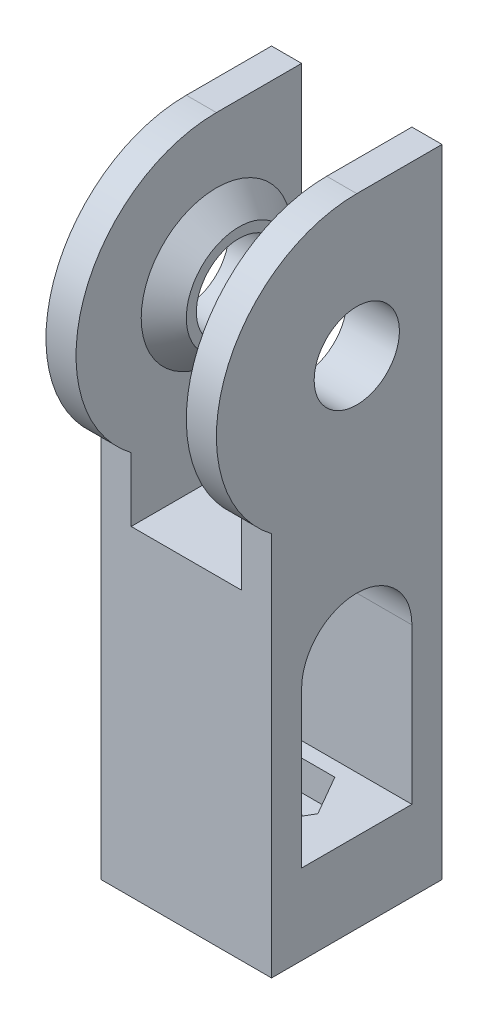
SolidWorks part; units mm, degrees
ref_plane "Front Plane" through (0, 0, 0) normal (0, 0, 1) x (1, 0, 0)
ref_plane "Top Plane" through (0, 0, 0) normal (0, 1, 0) x (1, 0, 0)
ref_plane "Right Plane" through (0, 0, 0) normal (1, 0, 0) x (0, 0, -1)
sketch "Sketch1" plane through (0, 0, 0) normal (0, 0, 1) x (1, 0, 0)
  line L0 (8.5, 32) -> (8.5, 0) construction
  line L1 (0, 0) -> (17, 0)
  line L2 (0, 0) -> (0, 63.5)
  line L3 (0, 63.5) -> (3, 63.5)
  line L4 (17, 0) -> (17, 63.5)
  line L5 (14, 63.5) -> (17, 63.5)
  line L6 (3, 63.5) -> (3, 32)
  line L7 (3, 32) -> (14, 32)
  line L8 (14, 63.5) -> (14, 32)
  dimension "D1" = 63.5
  dimension "D2" = 17
  dimension "D3" = 11
  dimension "D4" = 31.5
extrude "Boss-Extrude1" add sketch "Sketch1" along normal blind 22.5
sketch "Sketch2" plane through (17, 0, 0) normal (1, 0, 0) x (0, 0, -1)
  line L0 (-8.5, 8) -> (-8.5, 0) construction
  line L1 (-14, 23.5) -> (-3, 23.5) construction
  line L2 (-14, 23.5) -> (-14, 8)
  line L3 (-14, 8) -> (-3, 8)
  line L4 (-3, 23.5) -> (-3, 8)
  line L6 (-22.5, 0) -> (0, 0) construction
  line L7 (-8.5, 23.5) -> (-8.5, 49.5) construction
  line L8 (0, 0) -> (0, 63.5) construction
  line L9 (-22.5, 63.5) -> (-8.5, 63.5)
  line L10 (-22.5, 63.5) -> (0, 63.5) construction
  line L11 (-22.5, 63.5) -> (-22.5, 49.5)
  line L12 (-22.5, 0) -> (-22.5, 63.5) construction
  line L13 (-22.5, 0) -> (-22.5, 49.5)
  line L14 (-17, 38.3757) -> (-17, 0)
  line L15 (-22.5, 0) -> (-17, 0)
  arc A0 (-14, 23.5) -> (-3, 23.5) centre (-8.5, 23.5) cw
  circle A1 centre (-8.5, 49.5) radius 4.25 construction
  arc A2 (-8.5, 63.5) -> (-17, 38.3757) centre (-8.5, 49.5) ccw
  point P29 (-17, 19.1879)
  line M9 (0, 63.5) -> (-22.5, 63.5)
  line M10 (-22.5, 63.5) -> (-22.5, 0)
  line M11 (-22.5, 0) -> (0, 0)
  dimension "D3" = 5.5
  dimension "D5" = 8.5
  dimension "D7" = 28
  dimension "D1" = 11
  dimension "D2" = 15.5
  dimension "D4" = 8
  dimension "D6" = 26
  dimension "D8" = 8.5
  dimension "D9" = 5.5
extrude "Cut-Extrude1" cut sketch "Sketch2" against normal through all contours A2 L14 M10 M11 | A2 M9 M10 | A0 L2 L3 L4 | A1 region at (17, 17.9479, 8.5) region at (17, 20.9454, 19.8446) region at (17, 60.3728, 19.3728)
sketch "Sketch3" plane through (0, 0, 0) normal (0, -1, 0) x (1, 0, 0)
  line L0 (0, 0) -> (17, 17) construction
  circle A0 centre (8.5, 8.5) radius 2.3
  dimension "D1" = 4.6
extrude "Cut-Extrude2" cut sketch "Sketch3" against normal up to surface (8 mm away) up to face at (8.5, 8, 8.5)
sketch "Sketch4" plane through (0, 8, 0) normal (0, 1, 0) x (1, 0, 0)
  line L1 (3.8812, -8.5) -> (6.1906, -12.5)
  line L2 (6.1906, -12.5) -> (10.8094, -12.5)
  line L3 (10.8094, -12.5) -> (13.1188, -8.5)
  line L4 (13.1188, -8.5) -> (10.8094, -4.5)
  line L5 (10.8094, -4.5) -> (6.1906, -4.5)
  line L6 (6.1906, -4.5) -> (3.8812, -8.5)
  circle A0 centre (8.5, -8.5) radius 4 construction
  dimension "D1" = 8
extrude "Cut-Extrude3" cut sketch "Sketch4" against normal blind 3
sketch "Sketch5" plane through (14, 0, 0) normal (-1, 0, 0) x (0, 0, 1)
  circle A0 centre (8.5, 49.5) radius 7.5
  dimension "D1" = 15
ref_plane "Plane1" through (11.75, 0, 0) normal (-1, 0, 0) x (0, 0, 1)
sketch "Sketch6" plane through (11.75, 0, 0) normal (-1, 0, 0) x (0, 0, 1)
  circle A0 centre (8.5, 49.5) radius 5.25
  dimension "D1" = 10.5
loft "Loft1" add profiles "Sketch5", "Sketch6" connector at (14, 42, 8.5) connector at (11.75, 44.25, 8.5)
ref_plane "Plane2" through (8.5, 0, 0) normal (-1, 0, 0) x (0, 0, 1)
mirror "Mirror1" about plane through (8.5, 0, 0) normal (-1, 0, 0) of "Loft1"
sketch "Sketch7" plane through (17, 0, 0) normal (1, 0, 0) x (0, 0, -1)
  circle A0 centre (-8.5, 49.5) radius 4.25
  dimension "D1" = 8.5
extrude "Cut-Extrude4" cut sketch "Sketch7" against normal through all both and the other way through all
